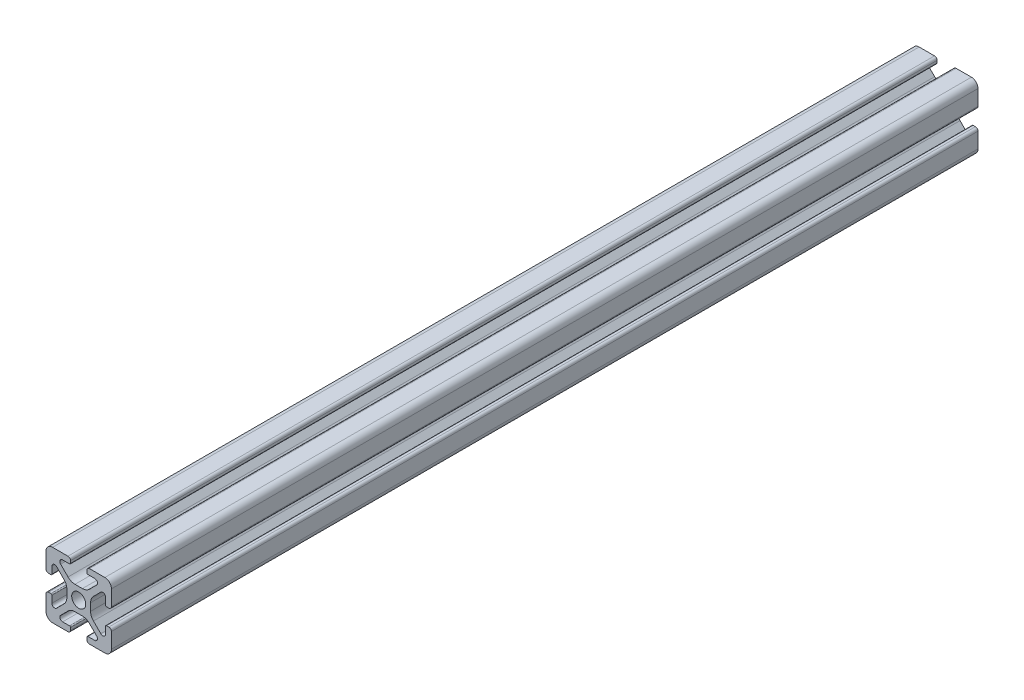
SolidWorks part; units mm, degrees
ref_plane "Front Plane" through (0, 0, 0) normal (0, 0, 1) x (1, 0, 0)
ref_plane "Top Plane" through (0, 0, 0) normal (0, 1, 0) x (1, 0, 0)
ref_plane "Right Plane" through (0, 0, 0) normal (1, 0, 0) x (0, 0, -1)
sketch "Sketch1" plane through (0, 0, 0) normal (0, 0, 1) x (1, 0, 0)
  line L2 (-9.9949, 7.9883) -> (-9.9949, 3.2893)
  line L3 (-7.9883, 9.9949) -> (-3.2893, 9.9949)
  line L4 (-2.5019, 9.2075) -> (-2.5019, 8.4963)
  line L5 (-2.8067, 8.1915) -> (-4.9149, 8.1915)
  line L6 (-5.5076, 6.7606) -> (-3.2528, 4.5058)
  line L7 (-6.7606, 5.5076) -> (-4.5058, 3.2528)
  line L8 (-8.1915, 4.9149) -> (-8.1915, 2.8067)
  line L9 (-8.4963, 2.5019) -> (-9.2075, 2.5019)
  line L11 (-1.1334, 3.6279) -> (1.1334, 3.6279)
  line L12 (-3.6279, 1.1334) -> (-3.6279, -1.1334)
  line L13 (8.4963, 2.5019) -> (9.2075, 2.5019)
  line L14 (8.1915, 4.9149) -> (8.1915, 2.8067)
  line L15 (9.9949, 7.9883) -> (9.9949, 3.2893)
  line L16 (7.9883, 9.9949) -> (3.2893, 9.9949)
  line L17 (2.5019, 9.2075) -> (2.5019, 8.4963)
  line L18 (2.8067, 8.1915) -> (4.9149, 8.1915)
  line L19 (3.6279, 1.1334) -> (3.6279, -1.1334)
  line L20 (5.5076, 6.7606) -> (3.2528, 4.5058)
  line L21 (6.7606, 5.5076) -> (4.5058, 3.2528)
  line L22 (-8.4963, -2.5019) -> (-9.2075, -2.5019)
  line L23 (-8.1915, -4.9149) -> (-8.1915, -2.8067)
  line L24 (-6.7606, -5.5076) -> (-4.5058, -3.2528)
  line L25 (-5.5076, -6.7606) -> (-3.2528, -4.5058)
  line L26 (-2.8067, -8.1915) -> (-4.9149, -8.1915)
  line L27 (-2.5019, -9.2075) -> (-2.5019, -8.4963)
  line L28 (-7.9883, -9.9949) -> (-3.2893, -9.9949)
  line L29 (-9.9949, -7.9883) -> (-9.9949, -3.2893)
  line L30 (9.9949, -7.9883) -> (9.9949, -3.2893)
  line L31 (7.9883, -9.9949) -> (3.2893, -9.9949)
  line L32 (2.5019, -9.2075) -> (2.5019, -8.4963)
  line L33 (2.8067, -8.1915) -> (4.9149, -8.1915)
  line L34 (5.5076, -6.7606) -> (3.2528, -4.5058)
  line L35 (6.7606, -5.5076) -> (4.5058, -3.2528)
  line L36 (8.1915, -4.9149) -> (8.1915, -2.8067)
  line L37 (8.4963, -2.5019) -> (9.2075, -2.5019)
  line L38 (-1.1334, -3.6279) -> (1.1334, -3.6279)
  circle A0 centre (0, 0) radius 2.1463
  arc A1 (-9.9949, 7.9883) -> (-7.9883, 9.9949) centre (-7.9883, 7.9883) cw
  arc A2 (-6.7606, 5.5076) -> (-8.1915, 4.9149) centre (-7.3533, 4.9149) ccw
  arc A3 (-4.9149, 8.1915) -> (-5.5076, 6.7606) centre (-4.9149, 7.3533) ccw
  arc A4 (-3.2893, 9.9949) -> (-2.5019, 9.2075) centre (-3.2893, 9.2075) cw
  arc A5 (-9.9949, 3.2893) -> (-9.2075, 2.5019) centre (-9.2075, 3.2893) ccw
  arc A6 (-8.1915, 2.8067) -> (-8.4963, 2.5019) centre (-8.4963, 2.8067) cw
  arc A7 (-2.5019, 8.4963) -> (-2.8067, 8.1915) centre (-2.8067, 8.4963) cw
  arc A8 (-1.1334, 3.6279) -> (-3.2528, 4.5058) centre (-1.1334, 6.6251) cw
  arc A9 (-3.6279, 1.1334) -> (-4.5058, 3.2528) centre (-6.6251, 1.1334) ccw
  arc A10 (8.1915, 2.8067) -> (8.4963, 2.5019) centre (8.4963, 2.8067) ccw
  arc A11 (9.9949, 3.2893) -> (9.2075, 2.5019) centre (9.2075, 3.2893) cw
  arc A12 (9.9949, 7.9883) -> (7.9883, 9.9949) centre (7.9883, 7.9883) ccw
  arc A13 (3.2893, 9.9949) -> (2.5019, 9.2075) centre (3.2893, 9.2075) ccw
  arc A14 (2.5019, 8.4963) -> (2.8067, 8.1915) centre (2.8067, 8.4963) ccw
  arc A15 (1.1334, 3.6279) -> (3.2528, 4.5058) centre (1.1334, 6.6251) ccw
  arc A16 (3.6279, 1.1334) -> (4.5058, 3.2528) centre (6.6251, 1.1334) cw
  arc A17 (6.7606, 5.5076) -> (8.1915, 4.9149) centre (7.3533, 4.9149) cw
  arc A18 (4.9149, 8.1915) -> (5.5076, 6.7606) centre (4.9149, 7.3533) cw
  arc A19 (-3.6279, -1.1334) -> (-4.5058, -3.2528) centre (-6.6251, -1.1334) cw
  arc A20 (-1.1334, -3.6279) -> (-3.2528, -4.5058) centre (-1.1334, -6.6251) ccw
  arc A21 (-2.5019, -8.4963) -> (-2.8067, -8.1915) centre (-2.8067, -8.4963) ccw
  arc A22 (-8.1915, -2.8067) -> (-8.4963, -2.5019) centre (-8.4963, -2.8067) ccw
  arc A23 (-9.9949, -3.2893) -> (-9.2075, -2.5019) centre (-9.2075, -3.2893) cw
  arc A24 (-3.2893, -9.9949) -> (-2.5019, -9.2075) centre (-3.2893, -9.2075) ccw
  arc A25 (-4.9149, -8.1915) -> (-5.5076, -6.7606) centre (-4.9149, -7.3533) cw
  arc A26 (-6.7606, -5.5076) -> (-8.1915, -4.9149) centre (-7.3533, -4.9149) cw
  arc A27 (-9.9949, -7.9883) -> (-7.9883, -9.9949) centre (-7.9883, -7.9883) ccw
  arc A28 (9.9949, -7.9883) -> (7.9883, -9.9949) centre (7.9883, -7.9883) cw
  arc A29 (6.7606, -5.5076) -> (8.1915, -4.9149) centre (7.3533, -4.9149) ccw
  arc A30 (4.9149, -8.1915) -> (5.5076, -6.7606) centre (4.9149, -7.3533) ccw
  arc A31 (3.2893, -9.9949) -> (2.5019, -9.2075) centre (3.2893, -9.2075) cw
  arc A32 (9.9949, -3.2893) -> (9.2075, -2.5019) centre (9.2075, -3.2893) ccw
  arc A33 (8.1915, -2.8067) -> (8.4963, -2.5019) centre (8.4963, -2.8067) cw
  arc A34 (2.5019, -8.4963) -> (2.8067, -8.1915) centre (2.8067, -8.4963) cw
  arc A35 (1.1334, -3.6279) -> (3.2528, -4.5058) centre (1.1334, -6.6251) cw
  arc A36 (3.6279, -1.1334) -> (4.5058, -3.2528) centre (6.6251, -1.1334) ccw
extrude "Boss-Extrude1" add sketch "Sketch1" along normal mid plane 264.8204
